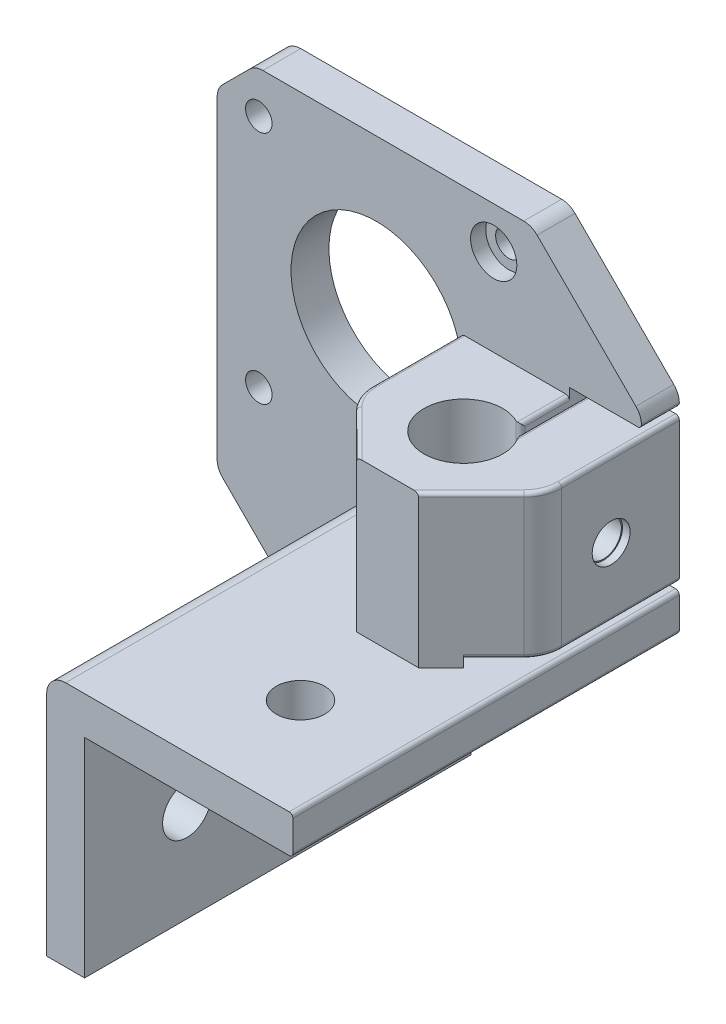
SolidWorks part; units mm, degrees
ref_plane "XY" through (0, 0, 0) normal (0, 0, 1) x (1, 0, 0)
ref_plane "XZ" through (0, 0, 0) normal (0, 1, 0) x (1, 0, 0)
ref_plane "YZ" through (0, 0, 0) normal (1, 0, 0) x (0, 0, -1)
sketch "Sketch1" plane through (0, 0, 0) normal (0, 0, 1) x (1, 0, 0)
  line L0 (-13.5, 34.75) -> (-28, 20.25)
  line L1 (28, 34.75) -> (23, 34.75) construction
  line L2 (28, 34.75) -> (28, 29.75) construction
  line L3 (28, -34.75) -> (7, -34.75) construction
  line L4 (-28, 34.75) -> (-28, 20.25) construction
  line L5 (28, 34.75) -> (-28, -34.75) construction
  line L6 (28, -34.75) -> (-28, 34.75) construction
  line L7 (-0.5, -7.25) -> (-28, -7.25)
  line L8 (-0.5, -7.25) -> (-0.5, -34.75)
  line L9 (-0.5, -34.75) -> (-28, -34.75) construction
  line L10 (-28, -7.25) -> (-28, -34.75) construction
  line L11 (-0.5, -7.25) -> (-28, -34.75) construction
  line L12 (-0.5, -34.75) -> (-28, -7.25) construction
  line L13 (-28, 20.25) -> (-28, -7.25)
  line L14 (-13.5, 34.75) -> (-28, 34.75) construction
  line L15 (23, 34.75) -> (28, 29.75)
  line L16 (23, 34.75) -> (-13.5, 34.75)
  line L17 (28, 29.75) -> (28, -13.75)
  line L18 (28, -13.75) -> (7, -34.75)
  line L19 (7, -34.75) -> (-0.5, -34.75)
  line L20 (28, -13.75) -> (28, -34.75) construction
  line L21 (7, 13.75) -> (7, 41.9826) construction
  line L22 (7, 13.75) -> (59.2876, 13.75) construction
  circle A0 centre (7, 13.75) radius 11.25
  circle A1 centre (-8.5, 29.25) radius 1.75
  circle A2 centre (22.5, 29.25) radius 1.75
  circle A3 centre (22.5, -1.75) radius 1.75
  point P0 (0, 0)
  point P5 (-14.25, -21)
  dimension "D11" = 22.5
  dimension "D14" = 3.5
  dimension "D1" = 69.5
  dimension "D2" = 56
  dimension "D3" = 27.5
  dimension "D4" = 27.5
  dimension "D5" = 14.5
  dimension "D6" = 14.5
  dimension "D7" = 5
  dimension "D8" = 5
  dimension "D9" = 21
  dimension "D10" = 21
  dimension "D12" = 21
  dimension "D13" = 21
  dimension "D15" = 15.5
  dimension "D16" = 15.5
extrude "Boss-Extrude1" add sketch "Sketch1" along normal blind 5
sketch "Sketch2" plane through (0, 0, 5) normal (0, 0, 1) x (1, 0, 0)
  line L0 (-28, -7.25) -> (-0.5, -7.25) construction
  line L1 (-0.5, -7.25) -> (-0.5, -34.75) construction
  line L2 (-28, -7.25) -> (-0.5, -7.25)
  line L3 (-0.5, -7.25) -> (-0.5, -34.75)
  line L4 (-28, -2.25) -> (4.5, -2.25)
  line L5 (4.5, -2.25) -> (4.5, -34.75)
  line L6 (-28, -2.25) -> (-28, -7.25)
  line L7 (-0.5, -34.75) -> (4.5, -34.75)
  dimension "D1" = 5
extrude "Boss-Extrude2" add sketch "Sketch2" along normal blind 46
sketch "Sketch3" plane through (0, -2.25, 0) normal (0, 1, 0) x (1, 0, 0)
  line L0 (-28, -5) -> (-28, -17.6)
  line L1 (4.5, -5) -> (-28, -5) construction
  line L2 (-28, -51) -> (-28, -5) construction
  line L3 (-28, -17.6) -> (-19.6, -26)
  line L4 (-19.6, -26) -> (-11.4, -26)
  line L5 (-11.4, -26) -> (-4.2, -18.8)
  line L7 (-4.2, -18.8) -> (-4.2, -5)
  line L8 (-4.2, -5) -> (-18.5, -5)
  line L9 (-18.5, -5) -> (-18.5, -11.7526)
  line L10 (-28, -5) -> (-19.5, -5)
  line L11 (-19.5, -5) -> (-19.5, -12.6774)
  line L12 (-15.5, -16) -> (-15.5, -32.7142) construction
  arc A0 (-19.5, -12.6774) -> (-18.5, -11.7526) centre (-15.5, -16) ccw
  dimension "D1" = 8.5
  dimension "D5" = 5.2
  dimension "D2" = 14.3
  dimension "D3" = 1
  dimension "D4" = 21
  dimension "D6" = 11
  dimension "D7" = 15.5
  dimension "D8" = 135
  dimension "D9" = 135
  dimension "D10" = 8.2
  dimension "D11" = 4.1
extrude "Boss-Extrude3" add sketch "Sketch3" along normal blind 20
sketch "Sketch4" plane through (0, -2.25, 0) normal (0, 1, 0) x (1, 0, 0)
  line L0 (-28, -51) -> (-28, 0) construction
  line L1 (-28, -17.6) -> (-28, 0)
  line L2 (-28, 0) -> (-0.5, 0) construction
  line L3 (-28, 0) -> (-18.5, 0)
  line L4 (-18.5, -5) -> (-18.5, -11.7526) construction
  line L5 (-18.5, 0) -> (-18.5, -11.7526)
  line L6 (-28, -17.6) -> (-19.6, -26) construction
  line L7 (-28, -17.6) -> (-22.55, -23.05)
  line L8 (-15.5, -16) -> (-30.5819, -31.0819) construction
  line L9 (-15.5, -16) -> (-44.7425, -16) construction
  line L10 (-22.55, -23.05) -> (-19.177, -19.677)
  arc A1 (-18.5, -11.7526) -> (-19.177, -19.677) centre (-15.5, -16) ccw
  dimension "D1" = 45
extrude "Cut-Extrude1" cut sketch "Sketch4" along normal blind 1
sketch "Sketch5" plane through (0, 0, 5) normal (0, 0, 1) x (1, 0, 0)
  line L0 (-19.5, 17.75) -> (-28, 17.75) construction
  line L1 (-19.5, 17.75) -> (-19.5, -1.25) construction
  line L2 (-19.5, 17.75) -> (-28, 17.75)
  line L3 (-19.5, 17.75) -> (-19.5, -1.25)
  line L4 (-18.5, 18.75) -> (-18.5, -1.25)
  line L5 (-18.5, 18.75) -> (-28, 18.75)
  line L6 (-18.5, -1.25) -> (-19.5, -1.25)
  line L7 (-28, 18.75) -> (-28, 17.75)
  dimension "D1" = 1
extrude "Cut-Extrude2" cut sketch "Sketch5" against normal through all
sketch "Sketch6" plane through (4.5, 0, 0) normal (1, 0, 0) x (0, 0, -1)
  circle A0 centre (-16, -22.25) radius 2.7
  circle A1 centre (-37.5, -22.25) radius 3.2
  dimension "D1" = 5.4
  dimension "D2" = 6.4
  dimension "D3" = 21.5
  dimension "D4" = 16
  dimension "D5" = 22.25
extrude "Cut-Extrude3" cut sketch "Sketch6" against normal up to next
sketch "Sketch7" plane through (0, -2.25, 0) normal (0, 1, 0) x (1, 0, 0)
  circle A0 centre (-15.5, -16) radius 5.2
  circle A1 centre (-15.5, -37.5) radius 3.2
  dimension "D1" = 10.4
  dimension "D2" = 6.4
  dimension "D3" = 21.5
extrude "Cut-Extrude4" cut sketch "Sketch7" against normal up to next
sketch "Sketch8" plane through (0, 0, 5) normal (0, 0, 1) x (1, 0, 0)
  circle A0 centre (-8.5, 29.25) radius 3.05
  dimension "D1" = 6.1
extrude "Cut-Extrude5" cut sketch "Sketch8" against normal blind 2
ref_plane "Plane1" through (0, 7.75, 0) normal (0, 1, 0) x (1, 0, 0)
sketch "Sketch9" plane through (0, 7.75, 0) normal (0, 1, 0) x (1, 0, 0)
  line L0 (-38.1403, -9) -> (15.031, -9) construction
  line L1 (23, 0) -> (-13.5, 0) construction
  line L2 (-4.2, -9) -> (-4.2, -6)
  line L3 (-4.2, -18.8) -> (-4.2, -5) construction
  line L4 (-4.2, -18.8) -> (-4.2, -5) construction
  line L5 (-4.2, -6) -> (-7.2, -6)
  line L6 (-7.2, -6) -> (-7.2, -7.25)
  line L7 (-7.2, -7.25) -> (-23, -7.25)
  line L8 (-23, -7.25) -> (-23, -6.65)
  line L9 (-23, -6.65) -> (-27, -6.65)
  line L10 (-27, -6.65) -> (-27, -6.5)
  line L11 (-27, -6.5) -> (-28, -6.5)
  line L12 (-28, 0) -> (-28, -17.6) construction
  line L13 (-28, -6.5) -> (-28, -9)
  line L14 (-28, -9) -> (-4.2, -9)
  dimension "D1" = 9
  dimension "D2" = 3
  dimension "D3" = 1.75
  dimension "D4" = 3
  dimension "D5" = 1
  dimension "D6" = 4
  dimension "D7" = 2.5
  dimension "D8" = 2.35
revolve "Cut-Revolve1" cut sketch "Sketch9" angle 360 about L0
fillet "Fillet1" radius 2.5 7 edges at (4.5, -2.25, 28) (-28, 20.25, 2.5) (7, -34.75, 2.5) (28, -13.75, 2.5) (28, 29.75, 2.5) (23, 34.75, 2.5) (-13.5, 34.75, 2.5)
fillet "Fillet2" radius 5 2 edges at (-28, 8.25, 17.6) (-4.2, 7.75, 18.8)
fillet "Fillet3" radius 0.5 16 edges at (-8.5322, 17.75, 23.1322) (-4.5806, 17.75, 18.6423) (-23.0678, 17.75, 22.5322) (-27.6194, 17.75, 17.4423) (-24.5428, -1.25, 21.0572) (-27.6194, -1.25, 17.4423) (-19.5, -1.25, 6.3387) (-4.2, 17.75, 10.8645) (-18.5, 7.75, 11.7526) (-18.5, 17.75, 8.3763) (-19.5, 17.75, 6.3387) (-28, 17.75, 7.7645) (-28, -1.25, 7.7645) (-28, 18.75, 2.5) (-28, -7.25, 25.5)
mirror "Mirror1" about plane through (0, 0, 0) normal (1, 0, 0) of bodies 126
delete or keep bodies "Body-Delete1" type delete bodies bodies 126
